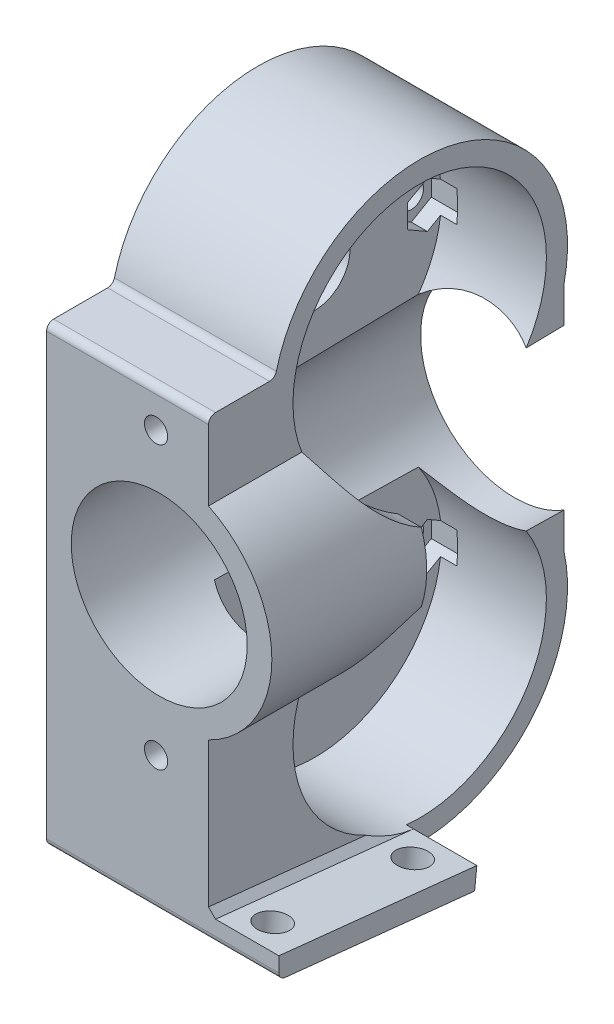
SolidWorks part; units mm, degrees
ref_plane "Front Plane" through (0, 0, 0) normal (0, 0, 1) x (1, 0, 0)
ref_plane "Top Plane" through (0, 0, 0) normal (0, 1, 0) x (1, 0, 0)
ref_plane "Right Plane" through (0, 0, 0) normal (1, 0, 0) x (0, 0, -1)
sketch "Sketch1" plane through (0, 0, 0) normal (1, 0, 0) x (0, 0, -1)
  line L1 (-30, 65) -> (30, 65)
  line L2 (-30, 65) -> (-30, -65)
  line L3 (-30, -65) -> (30, -65)
  line L4 (30, 65) -> (30, -65)
  line L5 (-30, 65) -> (30, -65) construction
  line L6 (-30, -65) -> (30, 65) construction
  point P0 (0, 0)
  dimension "D1" = 60
  dimension "D2" = 130
extrude "Boss-Extrude1" add sketch "Sketch1" along normal blind 32
sketch "Sketch2" plane through (32, 0, 0) normal (1, 0, 0) x (0, 0, -1)
  line L0 (0, 5) -> (0, -5)
  line L3 (0, 21) -> (0, 3) construction
  line L4 (0, -3) -> (0, -21) construction
  circle A0 centre (0, 21) radius 18
  circle A1 centre (0, -21) radius 18
  circle A2 centre (0, 21) radius 16 construction
  circle A3 centre (0, -21) radius 16 construction
  point P3 (0, 0)
  point P5 (0, 0)
  point P14 (0, 0)
  dimension "D1" = 36
  dimension "D2" = 32
  dimension "D3" = 10
extrude "Cut-Extrude1" cut sketch "Sketch2" against normal offset from surface (23.9 mm away) 23.9 contours A0 | A1 region at (32, -21, 0) region at (32, 21, 0) up to face at (32, 0, 0)
sketch "Sketch3" plane through (32, 0, 0) normal (1, 0, 0) x (0, 0, -1)
  circle A0 centre (0, 21) radius 5
  circle A1 centre (0, -21) radius 5
  dimension "D1" = 10
extrude "Cut-Extrude2" cut sketch "Sketch3" against normal through all
sketch "Sketch4" plane through (0, 0, 30) normal (0, 0, 1) x (1, 0, 0)
  line L0 (0, 0) -> (32, 0) construction
  line L1 (32, 65) -> (32, -65) construction
  circle A0 centre (16, 0) radius 12.5
  dimension "D1" = 25
sketch "Sketch5" plane through (0, 0, -30) normal (0, 0, -1) x (-1, 0, 0)
  circle A0 centre (-16, 0) radius 13.5
  dimension "D1" = 27
loft "Cut-Loft1" cut profiles "Sketch5", "Sketch4" connector at (29.5, -0.0095, -30) connector at (28.5, 0, 30)
sketch "Sketch6" plane through (0, 0, 0) normal (-1, 0, 0) x (0, 0, 1)
  circle A0 centre (0, 21) radius 13.875
  circle A1 centre (0, -21) radius 13.875
  dimension "D1" = 27.75
extrude "Cut-Extrude3" cut sketch "Sketch6" against normal offset from surface (5.05 mm away) 3.05 up to face at (8.1, 24.8137, -7.168)
sketch "Sketch8" plane through (0, 0, 30) normal (0, 0, 1) x (1, 0, 0)
  line L0 (23, 65) -> (23, 14.3875)
  line L1 (32, 65) -> (0, 65) construction
  line L2 (23, 65) -> (32, 65)
  line L3 (32, 65) -> (32, -65)
  line L4 (32, -65) -> (23, -65)
  line L5 (32, -65) -> (0, -65) construction
  line L6 (23, -65) -> (23, -14.3875)
  arc A0 (32, 0) -> (23, 14.3875) centre (16, 0) ccw
  arc A1 (23, -14.3875) -> (32, 0) centre (16, 0) ccw
  line M6 (0, -65) -> (32, -65)
  line M7 (32, -65) -> (32, 65)
  line M8 (32, 65) -> (0, 65)
  dimension "D1" = 9
extrude "Cut-Extrude8" cut sketch "Sketch8" against normal through all contours A0 L3 L0 M8 | A1 L6 M6 M7 region at (27.65, 37.5537, 30) region at (27.65, -37.5537, 30)
sketch "Sketch7" plane through (23, 0, 0) normal (-1, 0, 0) x (0, 0, 1)
  line L1 (18, 65) -> (-30, 65)
  line L2 (18, 65) -> (18, 17)
  line L3 (18, -65) -> (-30, -65)
  line L4 (-30, 65) -> (-30, -65)
  line L5 (30, -65) -> (-30, -65) construction
  line L6 (-30, 65) -> (30, 65) construction
  line L8 (-30, 65) -> (-30, 14.3875) construction
  line L9 (18, 17) -> (8, 11.2265)
  line L10 (8, 11.2265) -> (8, -11.2265)
  line L11 (8, -11.2265) -> (18, -17)
  line L12 (18, -17) -> (18, -65)
  dimension "D1" = 48
  dimension "D2" = 120
  dimension "D3" = 10
  dimension "D4" = 34
extrude "Cut-Extrude7" cut sketch "Sketch7" against normal through all
sketch "Sketch9" plane through (23, 0, 0) normal (1, 0, 0) x (0, 0, -1)
  line L0 (-30, -38.9625) -> (-30, -65)
  line L1 (-16.7414, 14.3875) -> (-30, 14.3875) construction
  line L2 (-30, -65) -> (-30, -14.3875) construction
  line L3 (-25.3415, -36.4357) -> (17.5288, -40.9415) construction
  line L4 (-30, -65) -> (30, -65)
  line L5 (30, 65) -> (30, 11.5434) construction
  line L6 (-30, 65) -> (30, 65)
  line L7 (-30, 65) -> (-30, 25.3875)
  line L8 (-30, 65) -> (-30, 14.3875) construction
  line L9 (30, 65) -> (30, 16.5004)
  line L10 (30, -65) -> (30, -16.5004)
  line L11 (30, -65) -> (30, 65) construction
  line L12 (-30, -12.5) -> (30, -13.5) construction
  line L13 (-2.1951, -41.885) -> (-30, -38.9625)
  line L14 (30, -16.5004) -> (20.4768, -16.3417)
  line L15 (-2.1951, -41.885) -> (-30, -41.885) construction
  line L16 (-30, 25.3875) -> (-20.5366, 25.3875)
  line L17 (20.4768, 16.3417) -> (30, 16.5004)
  line L18 (30, -13.5) -> (30, 13.5) construction
  line L19 (30, -13.5) -> (30, 13.5) construction
  line L20 (-30, 12.5) -> (-30, -12.5) construction
  line L21 (-30, 12.5) -> (-30, -12.5) construction
  line L22 (-30, 12.5) -> (30, 13.5) construction
  arc A0 (-14.2657, -10.0232) -> (14.7137, -10.6314) centre (0, -21) ccw construction
  arc A1 (20.4768, -16.3417) -> (-2.1951, -41.885) centre (0, -21) cw
  arc A2 (-14.2657, -10.0232) -> (14.7137, -10.6314) centre (0, -21) ccw construction
  arc A4 (17.1659, 8.9033) -> (-16.6433, 8.1937) centre (0, 21) ccw
  arc A5 (20.4768, 16.3417) -> (-20.5366, 25.3875) centre (0, 21) ccw
  point P16 (7.9918, -40.4199)
  point P40 (0, -42.1156)
  point P41 (2.0275, -42.1156)
  dimension "D3" = 3
  dimension "D6" = 3
  dimension "D1" = 6
  dimension "D2" = 3
  dimension "D4" = 3
  dimension "D5" = 11
  dimension "D7" = 3
extrude "Cut-Extrude9" cut sketch "Sketch9" against normal through all
sketch "Sketch10" plane through (0, 0, 30) normal (0, 0, 1) x (1, 0, 0)
  line L0 (15.55, 20) -> (15.55, -20) construction
  line L1 (15.55, 20) -> (15.55, 24.5116) construction
  line L2 (3.5, 0) -> (28.5, 0) construction
  line L3 (8.1, 10.0232) -> (8.1, 39) construction
  line L4 (8.1, 10.0232) -> (8.1, 39) construction
  line L5 (8.1, 24.5116) -> (23, 24.5116) construction
  line L6 (23, 25.3875) -> (23, 14.3875) construction
  circle A0 centre (16, 0) radius 12.5 construction
  circle A1 centre (15.55, 20) radius 1.65
  circle A2 centre (15.55, -20) radius 1.65
  point P5 (15.55, 0)
  point P20 (15.55, -20)
  point P26 (15.55, 20)
  dimension "D1" = 3.3
  dimension "D2" = 40
extrude "Cut-Extrude10" cut sketch "Sketch10" against normal blind 18
ref_plane "Plane1" through (0, 0, 15) normal (0, 0, 1) x (1, 0, 0)
sketch "Sketch11" plane through (0, 0, 15) normal (0, 0, 1) x (1, 0, 0)
  line L1 (17.1954, 17.15) -> (18.8409, 20)
  line L2 (18.8409, 20) -> (17.1954, 22.85)
  line L3 (17.1954, 22.85) -> (13.9046, 22.85)
  line L4 (13.9046, 22.85) -> (12.2591, 20)
  line L5 (12.2591, 20) -> (13.9046, 17.15)
  line L6 (13.9046, 17.15) -> (17.1954, 17.15)
  line L7 (17.1954, -22.85) -> (18.8409, -20)
  line L8 (18.8409, -20) -> (17.1954, -17.15)
  line L9 (17.1954, -17.15) -> (13.9046, -17.15)
  line L10 (13.9046, -17.15) -> (12.2591, -20)
  line L11 (12.2591, -20) -> (13.9046, -22.85)
  line L12 (13.9046, -22.85) -> (17.1954, -22.85)
  circle A0 centre (15.55, 20) radius 2.85 construction
  circle A1 centre (15.55, -20) radius 2.85 construction
  dimension "D1" = 5.7
extrude "Cut-Extrude11" cut sketch "Sketch11" along normal offset from surface (10 mm away) 5 up to face at (17.2, -20, 30)
sketch "Sketch12" plane through (0, 0, 0) normal (1, 0, 0) x (0, 0, -1)
  line L1 (16, -21) -> (-16, -21) construction
  line L2 (16, -21) -> (16, 21) construction
  line L3 (16, 21) -> (-16, 21) construction
  line L4 (-16, -21) -> (-16, 21) construction
  line L5 (16, -21) -> (-16, 21) construction
  line L6 (16, 21) -> (-16, -21) construction
  circle A1 centre (0, -21) radius 13.875 construction
  circle A2 centre (0, 21) radius 13.875 construction
  circle A3 centre (0, -21) radius 13.875 construction
  circle A4 centre (0, 21) radius 13.875 construction
  circle A5 centre (16, 21) radius 1.75
  circle A6 centre (-16, 21) radius 1.75
  circle A7 centre (16, -21) radius 1.75
  circle A8 centre (-16, -21) radius 1.75
  point P0 (0, 0)
  dimension "D1" = 3.5
  dimension "D2" = 32
extrude "Cut-Extrude13" cut sketch "Sketch12" along normal through all
ref_plane "Plane2" through (5.8, 0, 0) normal (1, 0, 0) x (0, 0, -1)
sketch "Sketch13" plane through (5.8, 0, 0) normal (1, 0, 0) x (0, 0, -1)
  line L1 (-13.15, 19.3546) -> (-13.15, 22.6454)
  line L2 (-13.15, 22.6454) -> (-16, 24.2909)
  line L3 (-16, 24.2909) -> (-18.85, 22.6454)
  line L4 (-18.85, 22.6454) -> (-18.85, 19.3546)
  line L5 (-18.85, 19.3546) -> (-16, 17.7091)
  line L6 (-16, 17.7091) -> (-13.15, 19.3546)
  line L7 (13.15, 19.3546) -> (16, 17.7091)
  line L8 (16, 17.7091) -> (18.85, 19.3546)
  line L9 (18.85, 19.3546) -> (18.85, 22.6454)
  line L10 (18.85, 22.6454) -> (16, 24.2909)
  line L11 (16, 24.2909) -> (13.15, 22.6454)
  line L12 (13.15, 22.6454) -> (13.15, 19.3546)
  line L13 (-13.15, -22.6454) -> (-13.15, -19.3546)
  line L14 (-13.15, -19.3546) -> (-16, -17.7091)
  line L15 (-16, -17.7091) -> (-18.85, -19.3546)
  line L16 (-18.85, -19.3546) -> (-18.85, -22.6454)
  line L17 (-18.85, -22.6454) -> (-16, -24.2909)
  line L18 (-16, -24.2909) -> (-13.15, -22.6454)
  line L19 (13.15, -22.6454) -> (16, -24.2909)
  line L20 (16, -24.2909) -> (18.85, -22.6454)
  line L21 (18.85, -22.6454) -> (18.85, -19.3546)
  line L22 (18.85, -19.3546) -> (16, -17.7091)
  line L23 (16, -17.7091) -> (13.15, -19.3546)
  line L24 (13.15, -19.3546) -> (13.15, -22.6454)
  circle A0 centre (-16, 21) radius 2.85 construction
  circle A1 centre (16, 21) radius 2.85 construction
  circle A2 centre (-16, -21) radius 2.85 construction
  circle A3 centre (16, -21) radius 2.85 construction
  dimension "D1" = 5.7
extrude "Cut-Extrude14" cut sketch "Sketch13" along normal offset from surface (4.6 mm away) 2.3 up to face at (8.1, 21, -17.75) offset beyond the face yes
sketch "Sketch14" plane through (0, 0, -30) normal (0, 0, -1) x (-1, 0, 0)
  line L5 (0, -16.5004) -> (0, 16.5004)
  line L6 (0, 16.5004) -> (-23, 16.5004)
  line L7 (-23, 16.5004) -> (-23, 11.5434)
  line L8 (-23, -11.5434) -> (-23, -16.5004)
  line L9 (-23, -16.5004) -> (0, -16.5004)
  line L10 (0, -16.5004) -> (0, 16.5004)
  line L11 (0, 16.5004) -> (-23, 16.5004)
  line L12 (-23, 16.5004) -> (-23, 11.1911)
  line L13 (-23, -11.1911) -> (-23, -16.5004)
  line L14 (-23, -16.5004) -> (0, -16.5004)
  arc A1 (-23, -11.5434) -> (-23, 11.5434) centre (-16, 0) ccw
  arc A3 (-22.8444, -11.2869) -> (-22.8444, 11.2869) centre (-16, 0) ccw
  arc A4 (-23, -11.1911) -> (-23, 11.1911) centre (-16, 0) ccw
  point P2 (-23, 11.8648)
  point P4 (0, 0)
  point P11 (-23.0538, -12.1833)
  point P12 (0, 0)
  point P13 (-22.5266, 11.3584)
  point P15 (0, 0)
  point P17 (-21.8629, -11.7148)
  point P18 (-21.8145, 11.3088)
  point P20 (-21.6454, -11.5991)
  dimension "D1" = 0
  dimension "D2" = 0.3
extrude "Cut-Extrude15" cut sketch "Sketch14" against normal up to vertex (9.5232 mm away) up to point (0, 16.3417, -20.4768)
sketch "Sketch17" plane through (23, 0, 0) normal (1, 0, 0) x (0, 0, -1)
  line L0 (-30, -38.9625) -> (-30, -35.946)
  line L1 (-30, -38.9625) -> (-30, -14.3875) construction
  line L2 (-30, -35.946) -> (-1.8815, -38.9014)
  line L3 (-1.8815, -38.9014) -> (-2.1951, -41.885)
  line L4 (-2.1951, -41.885) -> (-30, -38.9625)
  arc A0 (-16.7414, -14.3875) -> (15.1324, -11.2526) centre (0, -21) ccw construction
  arc A1 (-17.8632, -23.2152) -> (17.8632, -23.2152) centre (0, -21) ccw construction
  point P5 (-2.1951, -38.8657)
  point P12 (-2.1951, -38.8657)
extrude "Boss-Extrude3" add sketch "Sketch17" along normal blind 10
sketch "Sketch18" plane through (0, -38.6719, 4.0646) normal (0, 0.9945, -0.1045) x (1, 0, 0)
  line L0 (33, -11.9416) -> (23, -11.9416) construction
  line L1 (33, 2.1951) -> (33, -26.0783) construction
  line L2 (23, 2.1951) -> (23, -26.0783) construction
  line L3 (28, -1.9416) -> (28, -21.9416) construction
  circle A0 centre (28, -1.9416) radius 2.2
  circle A1 centre (28, -21.9416) radius 2.2
  point P9 (28, -11.9416)
  dimension "D1" = 4.4
  dimension "D2" = 20
extrude "Cut-Extrude16" cut sketch "Sketch18" against normal through all
chamfer "Chamfer1" distance 1 angle 45 1 edges at (23, -37.4237, 15.9408)
fillet "Fillet1" radius 1 3 edges at (16.5, -38.9625, 30) (11.5, 25.3875, 20.5366) (11.5, 25.3875, 30)
